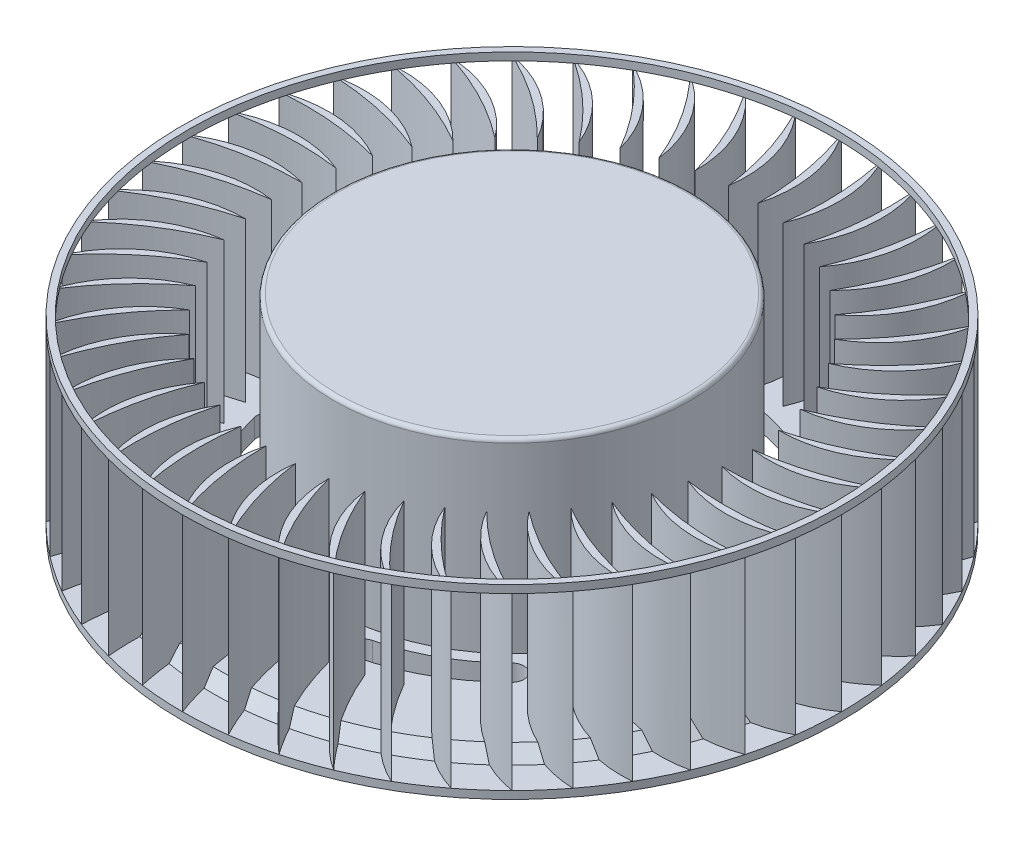
SolidWorks part; units mm, degrees
material "PET"
ref_plane "Спереди" through (0, 0, 0) normal (0, 0, 1) x (1, 0, 0)
ref_plane "Сверху" through (0, 0, 0) normal (0, 1, 0) x (1, 0, 0)
ref_plane "Справа" through (0, 0, 0) normal (1, 0, 0) x (0, 0, -1)
sketch "Эскиз1" plane through (0, 0, 0) normal (0, 1, 0) x (1, 0, 0)
  circle A0 centre (0, 0) radius 42.5
  dimension "D1" = 85
extrude "Бобышка-Вытянуть1" add sketch "Эскиз1" along normal blind 1
sketch "Эскиз2" plane through (0, 1, 0) normal (0, 1, 0) x (1, 0, 0)
  circle A0 centre (0, 0) radius 38.5
  circle A1 centre (0, 0) radius 42.5 construction
  dimension "D1" = 4
extrude "Бобышка-Вытянуть2" add sketch "Эскиз2" along normal blind 1.5
chamfer "Фаска1" distance 1.5 angle 45 1 edges at (0, 2.5, 38.5)
sketch "Эскиз3" plane through (0, 2.5, 0) normal (0, 1, 0) x (1, 0, 0)
  circle A0 centre (0, 0) radius 23
  dimension "D1" = 46
extrude "Бобышка-Вытянуть3" add sketch "Эскиз3" along normal offset from surface (24 mm away) 26.5 up to face at (0, 0, 42.5)
fillet "Скругление1" radius 0.5 1 edges at (0, 26.5, 23)
sketch "Эскиз4" plane through (0, 0, 0) normal (0, 1, 0) x (1, 0, 0)
  line L0 (0, 0) -> (0, 32.8652) construction
  line L1 (1.745, 36.059) -> (-34.8011, 29.6149) construction
  line L2 (0, 42.5) -> (2.3082, 29.4096) construction
  circle A0 centre (0, 0) radius 29.5 construction
  circle A1 centre (0, 0) radius 42.5 construction
  arc A2 (0, 42.5) -> (2.3082, 29.4096) centre (-34.8011, 29.6149) cw
  arc A3 (2.3082, 29.4096) -> (0, 42.5) centre (-12.6076, 33.5282) ccw
  point P9 (2.6313, 36.2153)
  dimension "D1" = 59
  dimension "D2" = 85
  dimension "D3" = 10
  dimension "D4" = 0.9
  dimension "D5" = 0.6
extrude "Бобышка-Вытянуть4" add sketch "Эскиз4" along normal blind 23
pattern_circular "Круговой массив1" count 48 over 360 about axis through (0, 0, 0) along (0, 1, 0) of "Бобышка-Вытянуть4"
sketch "Эскиз5" plane through (0, 0, 0) normal (0, -1, 0) x (1, 0, 0)
  circle A0 centre (0, 0) radius 20
  dimension "D1" = 40
extrude "Вырез-Вытянуть1" cut sketch "Эскиз5" against normal blind 1.2
chamfer "Фаска2" distance 1.2 angle 45 1 edges at (0, 0, -20)
sketch "Эскиз6" plane through (0, 1.2, 0) normal (0, -1, 0) x (1, 0, 0)
  circle A0 centre (0, 0) radius 20
  dimension "D1" = 40
extrude "Вырез-Вытянуть2" cut sketch "Эскиз6" against normal blind 8.5
sketch "Esboço1" plane through (0, 2.5, 0) normal (0, 1, 0) x (1, 0, 0)
  circle A0 centre (0, 0) radius 26 construction
  arc A1 (0, 26) -> (13.5393, 22.1966) centre (0, 0) cw construction
  arc A6 (14.3342, 23.4997) -> (0, 27.5265) centre (0, 0) ccw
  arc A7 (12.7444, 20.8934) -> (0, 24.4735) centre (0, 0) ccw
  arc A8 (12.7444, 20.8934) -> (14.3342, 23.4997) centre (13.5393, 22.1966) ccw
  arc A9 (0, 27.5265) -> (0, 24.4735) centre (0, 26) ccw
  arc A10 (18.3848, 18.3848) -> (25.2691, 6.1216) centre (0, 0) cw construction
  arc A11 (26.7526, 6.481) -> (19.4642, 19.4642) centre (0, 0) ccw
  arc A12 (23.7855, 5.7622) -> (17.3054, 17.3054) centre (0, 0) ccw
  arc A13 (23.7855, 5.7622) -> (26.7526, 6.481) centre (25.2691, 6.1216) ccw
  arc A14 (19.4642, 19.4642) -> (17.3054, 17.3054) centre (18.3848, 18.3848) ccw
  arc A15 (26, 0) -> (22.1966, -13.5393) centre (0, 0) cw construction
  arc A16 (23.4997, -14.3342) -> (27.5265, 0) centre (0, 0) ccw
  arc A17 (20.8934, -12.7444) -> (24.4735, 0) centre (0, 0) ccw
  arc A18 (20.8934, -12.7444) -> (23.4997, -14.3342) centre (22.1966, -13.5393) ccw
  arc A19 (27.5265, 0) -> (24.4735, 0) centre (26, 0) ccw
  arc A20 (18.3848, -18.3848) -> (6.1216, -25.2691) centre (0, 0) cw construction
  arc A21 (6.481, -26.7526) -> (19.4642, -19.4642) centre (0, 0) ccw
  arc A22 (5.7622, -23.7855) -> (17.3054, -17.3054) centre (0, 0) ccw
  arc A23 (5.7622, -23.7855) -> (6.481, -26.7526) centre (6.1216, -25.2691) ccw
  arc A24 (19.4642, -19.4642) -> (17.3054, -17.3054) centre (18.3848, -18.3848) ccw
  arc A25 (0, -26) -> (-13.5393, -22.1966) centre (0, 0) cw construction
  arc A26 (-14.3342, -23.4997) -> (0, -27.5265) centre (0, 0) ccw
  arc A27 (-12.7444, -20.8934) -> (0, -24.4735) centre (0, 0) ccw
  arc A28 (-12.7444, -20.8934) -> (-14.3342, -23.4997) centre (-13.5393, -22.1966) ccw
  arc A29 (0, -27.5265) -> (0, -24.4735) centre (0, -26) ccw
  arc A30 (-18.3848, -18.3848) -> (-25.2691, -6.1216) centre (0, 0) cw construction
  arc A31 (-26.7526, -6.481) -> (-19.4642, -19.4642) centre (0, 0) ccw
  arc A32 (-23.7855, -5.7622) -> (-17.3054, -17.3054) centre (0, 0) ccw
  arc A33 (-23.7855, -5.7622) -> (-26.7526, -6.481) centre (-25.2691, -6.1216) ccw
  arc A34 (-19.4642, -19.4642) -> (-17.3054, -17.3054) centre (-18.3848, -18.3848) ccw
  arc A35 (-26, 0) -> (-22.1966, 13.5393) centre (0, 0) cw construction
  arc A36 (-23.4997, 14.3342) -> (-27.5265, 0) centre (0, 0) ccw
  arc A37 (-20.8934, 12.7444) -> (-24.4735, 0) centre (0, 0) ccw
  arc A38 (-20.8934, 12.7444) -> (-23.4997, 14.3342) centre (-22.1966, 13.5393) ccw
  arc A39 (-27.5265, 0) -> (-24.4735, 0) centre (-26, 0) ccw
  arc A40 (-18.3848, 18.3848) -> (-6.1216, 25.2691) centre (0, 0) cw construction
  arc A41 (-6.481, 26.7526) -> (-19.4642, 19.4642) centre (0, 0) ccw
  arc A42 (-5.7622, 23.7855) -> (-17.3054, 17.3054) centre (0, 0) ccw
  arc A43 (-5.7622, 23.7855) -> (-6.481, 26.7526) centre (-6.1216, 25.2691) ccw
  arc A44 (-19.4642, 19.4642) -> (-17.3054, 17.3054) centre (-18.3848, 18.3848) ccw
  point P6 (7.0317, 25.0311)
  point P16 (22.6718, 12.7275)
  point P23 (25.0311, -7.0317)
  point P30 (12.7275, -22.6718)
  point P37 (-7.0317, -25.0311)
  point P44 (-22.6718, -12.7275)
  point P51 (-25.0311, 7.0317)
  point P58 (-12.7275, 22.6718)
  point P63 (0, 0)
  dimension "D1" = 52
  dimension "D2" = 8
extrude "Corte-extrusão1" cut sketch "Esboço1" against normal blind 10
sketch "Esboço3" plane through (0, 23, 0) normal (0, 1, 0) x (1, 0, 0)
  circle A0 centre (0, 0) radius 42.5
  circle A1 centre (0, 0) radius 41.6578
extrude "Ressalto-extrusão6" add sketch "Esboço3" along normal blind 1
scale "Escala1"
